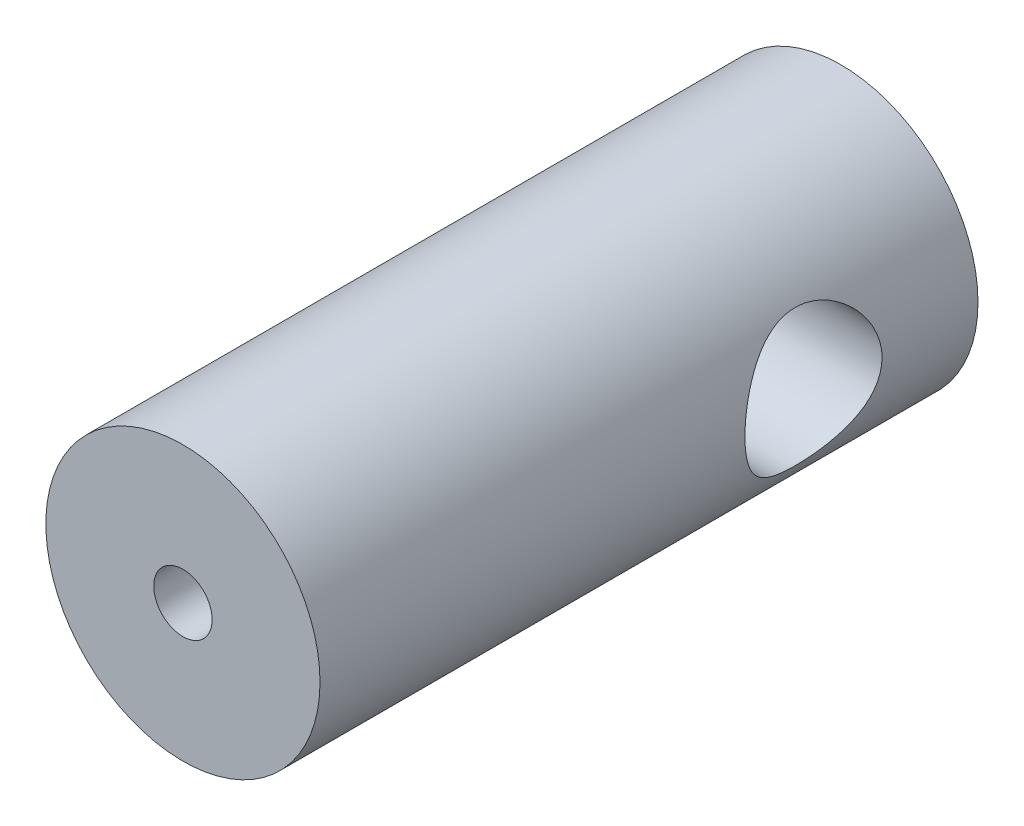
SolidWorks part; units mm, degrees
ref_plane "Front Plane" through (0, 0, 0) normal (0, 0, 1) x (1, 0, 0)
ref_plane "Top Plane" through (0, 0, 0) normal (0, 1, 0) x (1, 0, 0)
ref_plane "Right Plane" through (0, 0, 0) normal (1, 0, 0) x (0, 0, -1)
sketch "Sketch1" plane through (0, 0, 0) normal (0, 0, 1) x (1, 0, 0)
  circle A0 centre (0, 0) radius 6.35
  dimension "D1" = 12.7
extrude "Boss-Extrude1" add sketch "Sketch1" along normal blind 30.48
sketch "Sketch2" plane through (0, 0, 30.48) normal (0, 0, 1) x (1, 0, 0)
  circle A0 centre (0, 0) radius 1.905
  dimension "D1" = 3.81
extrude "Cut-Extrude1" [suppressed] cut sketch "Sketch2" against normal blind 12.7
sketch "Sketch3" plane through (0, 0, 0) normal (1, 0, 0) x (0, 0, -1)
  line L0 (-30.48, 6.35) -> (-30.48, -6.35) construction
  circle A0 centre (-7.62, 0) radius 3.175
  dimension "D2" = 6.35
  dimension "D1" = 22.86
extrude "Cut-Extrude2" cut sketch "Sketch3" against normal through all and the other way through all
hole_wizard "#6-32 Tapped Hole1" positions "Sketch5" profile "Sketch6" tap size "#6-32" standard "ANSI Inch"
sketch "Sketch5" plane through (0, 0, 30.48) normal (0, 0, 1) x (1, 0, 0)
  point P0 (0, 0)
sketch "Sketch6" plane through (0, 0, 30.48) normal (1, 0, 0) x (0, -1, 0)
  line L0 (0, 0) -> (0, 13.5127)
  line L1 (0, 13.5127) -> (1.3525, 12.7)
  line L2 (1.3525, 12.7) -> (1.3525, 0)
  line L5 (1.3525, 0) -> (0, 0)
  line L10 (0, 13.5127) -> (-1.3526, 12.7) construction
  line L11 (0, -6.35) -> (0, 107.95) construction
  dimension "Tap Drill Dia." = 2.7051
  dimension "Tap Drill Depth" = 12.7
  dimension "Drill Angle" = 118
cosmetic thread "Hole Thread1" parameters "D1"=1.0644, "D2"=3.5052
